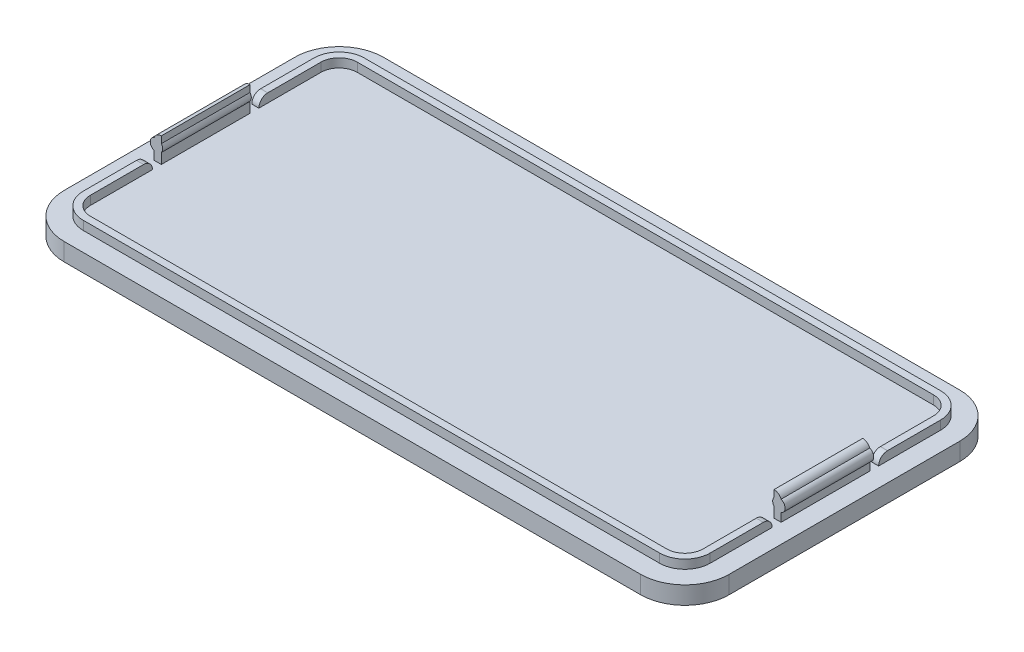
SolidWorks part; units mm, degrees
ref_plane "前视基准面" through (0, 0, 0) normal (0, 0, 1) x (1, 0, 0)
ref_plane "上视基准面" through (0, 0, 0) normal (0, 1, 0) x (1, 0, 0)
ref_plane "右视基准面" through (0, 0, 0) normal (1, 0, 0) x (0, 0, -1)
sketch "zero" plane through (0, 0, 0) normal (0, 1, 0) x (1, 0, 0)
  line L1 (-29.5, 15) -> (29.5, 15)
  line L2 (-32.5, 12) -> (-32.5, -12)
  line L3 (-29.5, -15) -> (29.5, -15)
  line L4 (32.5, 12) -> (32.5, -12)
  line L5 (-32.5, 15) -> (32.5, -15) construction
  line L6 (-32.5, -15) -> (32.5, 15) construction
  line L7 (-25.7, -15) -> (-14.5, -15)
  line L8 (-25.7, -15) -> (-25.7, -9.6569)
  line L9 (-25.7, -9.6569) -> (-14.5, -9.6569)
  line L10 (-14.5, -15) -> (-14.5, -9.6569)
  line L11 (5.2, -15) -> (12.7, -15)
  line L12 (5.2, -15) -> (5.2, -11)
  line L13 (5.2, -11) -> (12.7, -11)
  line L14 (12.7, -15) -> (12.7, -11)
  line L15 (17.8, -15) -> (25.3, -15)
  line L16 (17.8, -15) -> (17.8, -11)
  line L17 (17.8, -11) -> (25.3, -11)
  line L18 (25.3, -15) -> (25.3, -11)
  line L19 (-32.5, 7.7) -> (-19.5, 7.7)
  line L20 (-32.5, 7.7) -> (-32.5, -4.3)
  line L21 (-32.5, -4.3) -> (-19.5, -4.3)
  line L22 (-19.5, 7.7) -> (-19.5, -4.3)
  line L23 (-25.5, 14) -> (25.5, 14)
  line L24 (-25.5, 14) -> (-25.5, 8.8)
  line L25 (-25.5, 8.8) -> (25.5, 8.8)
  line L26 (25.5, 14) -> (25.5, 8.8)
  line L27 (-19.5, 7.2329) -> (-35.5, 7.2329)
  line L28 (-19.5, 7.2329) -> (-19.5, -3.7671)
  line L29 (-19.5, -3.7671) -> (-35.5, -3.7671)
  line L30 (-35.5, 7.2329) -> (-35.5, -3.7671)
  arc A0 (29.5, -15) -> (32.5, -12) centre (29.5, -12) ccw
  arc A1 (29.5, 15) -> (32.5, 12) centre (29.5, 12) cw
  arc A2 (-32.5, -12) -> (-29.5, -15) centre (-29.5, -12) ccw
  arc A3 (-29.5, 15) -> (-32.5, 12) centre (-29.5, 12) ccw
  circle A4 centre (-29, 11.4) radius 3
  circle A5 centre (-29, -11.5) radius 3
  circle A6 centre (29, 11.4) radius 3
  circle A7 centre (29, -11.5) radius 3
  circle A8 centre (-29, 11.4) radius 1.375
  circle A9 centre (-29, -11.5) radius 1.375
  circle A10 centre (29, -11.5) radius 1.375
  circle A11 centre (29, 11.4) radius 1.375
  point P0 (0, 0)
  dimension "D3" = 3
  dimension "D4" = 6
  dimension "D9" = 2.75
  dimension "D1" = 65
  dimension "D2" = 30
  dimension "D5" = 3.6
  dimension "D6" = 3.5
  dimension "D7" = 3.5
  dimension "D8" = 3.5
  dimension "D10" = 12
  dimension "D11" = 7.3
  dimension "D12" = 13
  dimension "D13" = 11.2
  dimension "D14" = 6.8
  dimension "D15" = 19.7
  dimension "D16" = 7.5
  dimension "D17" = 7.5
  dimension "D18" = 5.1
  dimension "D19" = 4
  dimension "D20" = 5.2
  dimension "D21" = 7
  dimension "D22" = 7
  dimension "D23" = 1
  dimension "D24" = 11
  dimension "D25" = 16
sketch "sugar" plane through (0, 0, 0) normal (0, 1, 0) x (1, 0, 0)
  line L1 (-29.5, 15) -> (29.5, 15)
  line L2 (-32.5, 12) -> (-32.5, -12)
  line L3 (-29.5, -15) -> (29.5, -15)
  line L4 (32.5, 12) -> (32.5, -12)
  line L5 (-32.5, 15) -> (32.5, -15) construction
  line L6 (-32.5, -15) -> (32.5, 15) construction
  line L7 (23.5, -11.5) -> (19.5, -11.5)
  line L8 (23.5, -11.5) -> (23.5, -13.9082)
  line L9 (23.5, -13.9082) -> (19.5, -13.9082)
  line L10 (19.5, -11.5) -> (19.5, -13.9082)
  line L11 (16, -11.0071) -> (8.5, -11.0071)
  line L12 (16, -11.0071) -> (16, -15)
  line L13 (16, -15) -> (8.5, -15)
  line L14 (8.5, -11.0071) -> (8.5, -15)
  line L15 (20.5, -13.9082) -> (22.5, -13.9082)
  line L16 (20.5, -13.9082) -> (20.5, -14.8173)
  line L17 (20.5, -14.8173) -> (22.5, -14.8173)
  line L18 (22.5, -13.9082) -> (22.5, -14.8173)
  arc A0 (29.5, 15) -> (32.5, 12) centre (29.5, 12) cw
  arc A1 (29.5, -15) -> (32.5, -12) centre (29.5, -12) ccw
  arc A2 (-32.5, -12) -> (-29.5, -15) centre (-29.5, -12) ccw
  arc A3 (-29.5, 15) -> (-32.5, 12) centre (-29.5, 12) ccw
  circle A4 centre (-29, 11.4) radius 3
  circle A5 centre (-29, 11.4) radius 1.375
  circle A6 centre (-29, -11.5) radius 3
  circle A7 centre (-29, -11.5) radius 1.375
  circle A8 centre (29, 11.4) radius 3
  circle A9 centre (29, 11.4) radius 1.375
  circle A10 centre (29, -11.5) radius 3
  circle A11 centre (29, -11.5) radius 1.375
  dimension "D3" = 3
  dimension "D1" = 65
  dimension "D2" = 30
  dimension "D4" = 9
  dimension "D5" = 4
  dimension "D6" = 3.5
  dimension "D7" = 7.5
  dimension "D8" = 2
  dimension "D9" = 1
sketch "case" plane through (0, 0, 0) normal (0, 1, 0) x (1, 0, 0)
  line L1 (-34.0422, 18) -> (30.9578, 18)
  line L2 (-39.0422, 13) -> (-39.0422, -13)
  line L3 (-34.0422, -18) -> (30.9578, -18)
  line L4 (35.9578, 13) -> (35.9578, -13)
  line L5 (-39.0422, 18) -> (35.9578, -18) construction
  line L6 (-39.0422, -18) -> (35.9578, 18) construction
  arc A0 (-39.0422, -13) -> (-34.0422, -18) centre (-34.0422, -13) ccw
  arc A1 (30.9578, -18) -> (35.9578, -13) centre (30.9578, -13) ccw
  arc A2 (30.9578, 18) -> (35.9578, 13) centre (30.9578, 13) cw
  arc A3 (-34.0422, 18) -> (-39.0422, 13) centre (-34.0422, 13) ccw
  point P0 (-1.5422, 0)
  point P3 (-1.5422, 0)
  dimension "D3" = 5
  dimension "D1" = 75
  dimension "D2" = 36
extrude "凸台-拉伸2" add sketch "case" along normal blind 2
sketch "草图2" plane through (0, 0, 0) normal (0, 1, 0) x (1, 0, 0)
  line L4 (-34.0422, -15.05) -> (30.9578, -15.05)
  line L5 (33.0078, -13) -> (33.0078, 13)
  line L6 (30.9578, 15.05) -> (-34.0422, 15.05)
  line L7 (-36.0922, 13) -> (-36.0922, -13)
  line L8 (33.8078, -13) -> (33.8078, 13)
  line L9 (30.9578, 15.85) -> (-34.0422, 15.85)
  line L10 (-36.8922, 13) -> (-36.8922, -13)
  line L11 (-34.0422, -15.85) -> (30.9578, -15.85)
  line L12 (33.8078, -13) -> (33.8078, 13)
  line L13 (30.9578, 15.85) -> (-34.0422, 15.85)
  line L14 (-36.8922, 13) -> (-36.8922, -13)
  line L15 (-34.0422, -15.85) -> (30.9578, -15.85)
  arc A4 (30.9578, -15.05) -> (33.0078, -13) centre (30.9578, -13) ccw
  arc A5 (33.0078, 13) -> (30.9578, 15.05) centre (30.9578, 13) ccw
  arc A6 (-34.0422, 15.05) -> (-36.0922, 13) centre (-34.0422, 13) ccw
  arc A7 (-36.0922, -13) -> (-34.0422, -15.05) centre (-34.0422, -13) ccw
  arc A8 (30.9578, -15.85) -> (33.8078, -13) centre (30.9578, -13) ccw
  arc A9 (33.8078, 13) -> (30.9578, 15.85) centre (30.9578, 13) ccw
  arc A10 (-34.0422, 15.85) -> (-36.8922, 13) centre (-34.0422, 13) ccw
  arc A11 (-36.8922, -13) -> (-34.0422, -15.85) centre (-34.0422, -13) ccw
  arc A12 (30.9578, -15.85) -> (33.8078, -13) centre (30.9578, -13) ccw
  arc A13 (33.8078, 13) -> (30.9578, 15.85) centre (30.9578, 13) ccw
  arc A14 (-34.0422, 15.85) -> (-36.8922, 13) centre (-34.0422, 13) ccw
  arc A15 (-36.8922, -13) -> (-34.0422, -15.85) centre (-34.0422, -13) ccw
  dimension "D1" = 2.15
  dimension "D2" = 0.8
ref_plane "基准面1" through (0, 2, 0) normal (0, 1, 0) x (1, 0, 0)
sketch "草图3" plane through (0, 2, 0) normal (0, 1, 0) x (1, 0, 0)
  line L4 (-34.0422, -15.05) -> (30.9578, -15.05)
  line L5 (33.0078, -13) -> (33.0078, 13)
  line L6 (30.9578, 15.05) -> (-34.0422, 15.05)
  line L7 (-36.0922, 13) -> (-36.0922, -13)
  line L8 (-34.0422, -15.05) -> (30.9578, -15.05)
  line L9 (33.0078, -13) -> (33.0078, 13)
  line L10 (30.9578, 15.05) -> (-34.0422, 15.05)
  line L11 (-36.0922, 13) -> (-36.0922, -13)
  line L12 (-36.8922, 13) -> (-36.8922, -13)
  line L13 (-34.0422, -15.85) -> (30.9578, -15.85)
  line L14 (33.8078, -13) -> (33.8078, 13)
  line L15 (30.9578, 15.85) -> (-34.0422, 15.85)
  line L16 (-36.8922, 13) -> (-36.8922, -13)
  line L17 (-34.0422, -15.85) -> (30.9578, -15.85)
  line L18 (33.8078, -13) -> (33.8078, 13)
  line L19 (30.9578, 15.85) -> (-34.0422, 15.85)
  arc A4 (30.9578, -15.05) -> (33.0078, -13) centre (30.9578, -13) ccw
  arc A5 (33.0078, 13) -> (30.9578, 15.05) centre (30.9578, 13) ccw
  arc A6 (-34.0422, 15.05) -> (-36.0922, 13) centre (-34.0422, 13) ccw
  arc A7 (-36.0922, -13) -> (-34.0422, -15.05) centre (-34.0422, -13) ccw
  arc A8 (30.9578, -15.05) -> (33.0078, -13) centre (30.9578, -13) ccw
  arc A9 (33.0078, 13) -> (30.9578, 15.05) centre (30.9578, 13) ccw
  arc A10 (-34.0422, 15.05) -> (-36.0922, 13) centre (-34.0422, 13) ccw
  arc A11 (-36.0922, -13) -> (-34.0422, -15.05) centre (-34.0422, -13) ccw
  arc A12 (-36.8922, -13) -> (-34.0422, -15.85) centre (-34.0422, -13) ccw
  arc A13 (30.9578, -15.85) -> (33.8078, -13) centre (30.9578, -13) ccw
  arc A14 (33.8078, 13) -> (30.9578, 15.85) centre (30.9578, 13) ccw
  arc A15 (-34.0422, 15.85) -> (-36.8922, 13) centre (-34.0422, 13) ccw
  arc A16 (-36.8922, -13) -> (-34.0422, -15.85) centre (-34.0422, -13) ccw
  arc A17 (30.9578, -15.85) -> (33.8078, -13) centre (30.9578, -13) ccw
  arc A18 (33.8078, 13) -> (30.9578, 15.85) centre (30.9578, 13) ccw
  arc A19 (-34.0422, 15.85) -> (-36.8922, 13) centre (-34.0422, 13) ccw
  dimension "D1" = 0
  dimension "D2" = 0
extrude "凸台-拉伸4" add sketch "草图3" along normal blind 1
ref_plane "基准面3" through (33.8078, 0, 0) normal (1, 0, 0) x (0, 0, -1)
sketch "草图7" plane through (0, 2, 0) normal (0, 1, 0) x (1, 0, 0)
  line L0 (-36.8922, 13) -> (-36.8922, -13) construction
  line L1 (-36.8922, 5) -> (-36.0922, 5)
  line L2 (-36.8922, 5) -> (-36.8922, -5)
  line L3 (-36.8922, -5) -> (-36.0922, -5)
  line L4 (-36.0922, 5) -> (-36.0922, -5)
  line L5 (-36.0922, 13) -> (-36.0922, -13) construction
  point P10 (-36.0922, 0)
  dimension "D1" = 5
  dimension "D2" = 10
extrude "凸台-拉伸8" add sketch "草图7" along normal blind 2.8
ref_plane "基准面5" through (0, 0, 5) normal (0, 0, 1) x (1, 0, 0)
sketch "草图8" plane through (0, 0, 5) normal (0, 0, 1) x (1, 0, 0)
  line L0 (-34.0422, 2) -> (-39.0422, 2) construction
  line L1 (-36.8922, 4.8) -> (-36.8922, 3) construction
  circle A0 centre (-36.6422, 3.6) radius 0.7
  dimension "D1" = 1.4
  dimension "D2" = 1.6
  dimension "D3" = 0.25
extrude "凸台-拉伸9" add sketch "草图8" against normal blind 10
fillet "圆角1" radius 0.85 1 edges at (-36.8922, 4.8, 0)
ref_plane "基准面7" through (-36.8922, 0, 0) normal (-1, 0, 0) x (0, 0, 1)
sketch "草图11" plane through (-36.8922, 0, 0) normal (-1, 0, 0) x (0, 0, 1)
  line L0 (-13, 2) -> (13, 2) construction
  line L1 (5, 3) -> (6, 3)
  line L2 (5, 3) -> (5, 2)
  line L3 (5, 2) -> (6, 2)
  line L4 (6, 3) -> (6, 2)
  line L6 (-5, 3) -> (-6, 3)
  line L7 (-5, 3) -> (-5, 2)
  line L8 (-5, 2) -> (-6, 2)
  line L9 (-6, 3) -> (-6, 2)
  dimension "D1" = 1
  dimension "D2" = 1
extrude "切除-拉伸1" cut sketch "草图11" against normal blind 1.2
fillet "圆角2" radius 1 2 edges at (-36.4922, 3, 6) (-36.4922, 3, -6)
ref_plane "基准面8" through (0, 0, 0) normal (0, -1, 0) x (-1, 0, 0)
sketch "草图12" plane through (0, 0, 0) normal (0, -1, 0) x (-1, 0, 0)
  line L76 (34.0422, -18) -> (-30.9578, -18) construction
  line L78 (39.0422, 13) -> (39.0422, -13) construction
  line B0 (-8.1993, 5.026) -> (-9.0198, 5.499)
  line B1 (-9.0198, 5.499) -> (-13.2767, 7.9551)
  line B2 (-13.2767, 7.9551) -> (-14.0973, 8.4339)
  line B3 (-15.8183, 8.4339) -> (-16.6389, 7.9551)
  line B4 (-16.6389, 7.9551) -> (-20.8958, 5.499)
  line B5 (-20.8958, 5.499) -> (-21.7165, 5.026)
  line B6 (-22.577, 3.5387) -> (-22.577, -3.2769)
  line B7 (-21.7165, -4.7643) -> (-20.8958, -5.2373)
  line B8 (-20.8958, -5.2373) -> (-16.6389, -7.6934)
  line B9 (-16.6389, -7.6934) -> (-15.8183, -8.172)
  line B10 (-14.0973, -8.172) -> (-13.2767, -7.6934)
  line B11 (-13.2767, -7.6934) -> (-9.0198, -5.2373)
  line B12 (-9.0198, -5.2373) -> (-8.1993, -4.7643)
  line B13 (-7.3388, -3.2769) -> (-7.3388, 3.5387)
  line B14 (-20.6223, 4.3479) -> (-15.3568, 7.391)
  line B15 (-14.5532, 7.391) -> (-9.3162, 4.3422)
  line B16 (-9.3105, 3.6413) -> (-14.3993, 0.5982)
  line B17 (-12.8208, -4.5591) -> (-13.4135, -4.8896)
  line B18 (-13.4705, -4.9865) -> (-13.4705, -6.6961)
  line B19 (-13.5274, -6.793) -> (-14.633, -7.4198)
  line B20 (-14.7983, -7.3229) -> (-14.7983, -2.046)
  line B21 (-14.7413, -1.9491) -> (-12.8607, -0.8835)
  line B22 (-8.9173, -4.2058) -> (-10.0114, -4.8269)
  line B23 (-10.1767, -4.7301) -> (-10.1767, -2.2169)
  line B24 (-10.1197, -2.1201) -> (-9.0256, -1.5046)
  line B25 (-8.8603, -1.6015) -> (-8.8603, -4.1089)
  line B26 (-12.8893, -3.5447) -> (-13.4135, -3.8069)
  line B27 (-13.4705, -3.6872) -> (-13.4705, -2.3423)
  line B28 (-13.4135, -2.2455) -> (-12.9234, -1.9719)
  line B29 (-3.344, 3.06) -> (-5.2189, 3.06)
  line B30 (-5.2189, 3.06) -> (-5.2189, -3.5048)
  line B31 (-5.2189, -3.5048) -> (-4.3868, -3.5048)
  line B32 (-4.3868, -3.5048) -> (-4.3868, -0.9005)
  line B33 (-4.3868, -0.9005) -> (-3.2984, -0.9005)
  line B34 (-3.4066, -0.2281) -> (-4.3868, -0.2281)
  line B35 (-4.3868, -0.2281) -> (-4.3868, 2.3876)
  line B36 (-4.3868, 2.3876) -> (-3.4408, 2.3876)
  line B37 (0.1948, 1.3618) -> (0.1948, -3.5048)
  line B38 (0.1948, -3.5048) -> (1.0098, -3.5048)
  line B39 (1.0098, -3.5048) -> (1.0098, 1.3618)
  line B40 (1.0098, 1.3618) -> (0.1948, 1.3618)
  line B41 (5.7169, 0.2847) -> (4.8849, 0.6153)
  line B42 (6.0417, 1.4017) -> (6.8396, 2.4047)
  line B43 (3.6084, -0.5586) -> (4.4575, -0.9177)
  line B44 (2.9074, -1.5673) -> (2.0014, -2.6729)
  line B45 (10.8229, 1.5898) -> (10.8229, -1.7497)
  line B46 (9.3811, -1.3621) -> (9.3811, 1.5898)
  line B47 (9.3811, 1.5898) -> (7.7912, 1.5898)
  line B48 (7.7912, 1.5898) -> (7.7912, -1.5616)
  line B49 (10.9711, -2.8039) -> (11.0052, -2.8039)
  line B50 (11.0052, -2.8039) -> (11.1193, -3.5048)
  line B51 (11.1193, -3.5048) -> (12.4185, -3.5048)
  line B52 (12.4185, -3.5048) -> (12.4185, 1.5898)
  line B53 (12.4185, 1.5898) -> (10.8229, 1.5898)
  line B54 (16.2708, -2.5019) -> (15.4673, -2.5019)
  line B55 (17.365, 0.4386) -> (18.1513, 0.4386)
  line B56 (18.1513, 0.4386) -> (18.1513, 1.5898)
  line B57 (18.1513, 1.5898) -> (16.2822, 1.5898)
  line B58 (14.0312, -1.4533) -> (14.0312, -1.4875)
  line B59 (13.9344, -3.3168) -> (13.9344, -3.3624)
  line B60 (15.4844, -3.7214) -> (15.9688, -3.7214)
  line B61 (18.6072, 1.0484) -> (19.1657, -0.0002)
  line B62 (21.411, -2.992) -> (21.4508, -2.992)
  line B63 (21.4508, -2.992) -> (21.5648, -3.5048)
  line B64 (21.5648, -3.5048) -> (22.8641, -3.5048)
  line B65 (22.8641, -3.5048) -> (22.8641, -0.6099)
  line B66 (21.2685, -1.1741) -> (21.2685, -1.989)
  line B67 (25.3545, 0.7065) -> (25.3203, 0.7065)
  line B68 (25.3203, 0.7065) -> (25.212, 1.5898)
  line B69 (25.212, 1.5898) -> (23.9127, 1.5898)
  line B70 (23.9127, 1.5898) -> (23.9127, -3.5048)
  line B71 (23.9127, -3.5048) -> (25.4969, -3.5048)
  line B72 (25.4969, -3.5048) -> (25.4969, -0.5928)
  line B73 (27.1552, 0.2392) -> (27.423, 1.6125)
  line B74 (-13.4135, -3.8069) -> (-13.4135, -4.8896)
  line B75 (-13.4705, -3.6872) -> (-13.4705, -4.9865)
  spline B76 degree 3 poles (-14.0973, 8.4339) (-14.3652, 8.582) (-14.6615, 8.6618) (-14.9578, 8.6618) knots 3 3 3 3 4 4 4 4
  spline B77 degree 3 poles (-14.9578, 8.6618) (-15.2541, 8.6618) (-15.5505, 8.582) (-15.8183, 8.4339) knots 4 4 4 4 5 5 5 5
  spline B78 degree 3 poles (-21.7165, 5.026) (-22.2464, 4.7183) (-22.577, 4.1485) (-22.577, 3.5387) knots 8 8 8 8 9 9 9 9
  spline B79 degree 3 poles (-22.577, -3.2769) (-22.577, -3.8923) (-22.2464, -4.4565) (-21.7165, -4.7643) knots 10 10 10 10 11 11 11 11
  spline B80 degree 3 poles (-15.8183, -8.172) (-15.5505, -8.3259) (-15.2541, -8.4) (-14.9578, -8.4) knots 14 14 14 14 15 15 15 15
  spline B81 degree 3 poles (-14.9578, -8.4) (-14.6615, -8.4) (-14.3652, -8.3259) (-14.0973, -8.172) knots 15 15 15 15 16 16 16 16
  spline B82 degree 3 poles (-8.1993, -4.7643) (-7.6636, -4.4565) (-7.3388, -3.8923) (-7.3388, -3.2769) knots 19 19 19 19 20 20 20 20
  spline B83 degree 3 poles (-7.3388, 3.5387) (-7.3388, 4.1485) (-7.6636, 4.7183) (-8.1993, 5.026) knots 21 21 21 21 22 22 22 22
  spline B84 degree 2 poles (-15.5106, 0.5982) (-20.6622, 3.5729) (-20.6736, 3.5786) knots 0 0 0 1 1 1
  spline B85 degree 3 poles (-20.6736, 3.5786) (-20.9414, 3.7723) (-20.9129, 4.1826) (-20.6223, 4.3479) knots 1 1 1 1 2 2 2 2
  spline B86 degree 3 poles (-15.3568, 7.391) (-15.1117, 7.5335) (-14.8039, 7.5335) (-14.5532, 7.391) knots 3 3 3 3 4 4 4 4
  spline B87 degree 3 poles (-9.3162, 4.3422) (-9.0484, 4.1883) (-9.0427, 3.8008) (-9.3105, 3.6413) knots 5 5 5 5 6 6 6 6
  spline B88 degree 3 poles (-14.3993, 0.5982) (-14.7413, 0.3987) (-15.1687, 0.3987) (-15.5106, 0.5982) knots 7 7 7 7 8 8 8 8
  spline B89 degree 3 poles (-13.4705, -6.6961) (-13.4705, -6.736) (-13.4876, -6.7702) (-13.5274, -6.793) knots 3 3 3 3 4 4 4 4
  spline B90 degree 3 poles (-14.633, -7.4198) (-14.7071, -7.4597) (-14.7983, -7.4084) (-14.7983, -7.3229) knots 5 5 5 5 6 6 6 6
  spline B91 degree 3 poles (-14.7983, -2.046) (-14.7983, -2.0061) (-14.7812, -1.9662) (-14.7413, -1.9491) knots 7 7 7 7 8 8 8 8
  spline B92 degree 3 poles (-12.8607, -0.8835) (-11.6412, -0.1939) (-10.6326, -0.0572) (-10.6326, -1.4249) knots 9 9 9 9 10 10 10 10
  spline B93 degree 3 poles (-10.6326, -1.4249) (-10.6326, -2.7412) (-11.6526, -3.898) (-12.8208, -4.5591) knots 10 10 10 10 11 11 11 11
  spline B94 degree 3 poles (-8.8603, -4.1089) (-8.8603, -4.1488) (-8.8831, -4.1887) (-8.9173, -4.2058) knots 0 0 0 0 1 1 1 1
  spline B95 degree 3 poles (-10.0114, -4.8269) (-10.0855, -4.8668) (-10.1767, -4.8155) (-10.1767, -4.7301) knots 2 2 2 2 3 3 3 3
  spline B96 degree 3 poles (-10.1767, -2.2169) (-10.1767, -2.1771) (-10.1539, -2.1429) (-10.1197, -2.1201) knots 4 4 4 4 5 5 5 5
  spline B97 degree 3 poles (-9.0256, -1.5046) (-8.9515, -1.4647) (-8.8603, -1.516) (-8.8603, -1.6015) knots 6 6 6 6 7 7 7 7
  spline B98 degree 3 poles (-9.5156, 0.1651) (-9.0768, 0.4158) (-8.7634, 0.3076) (-8.7634, -0.0914) (-8.7634, -0.4846) (-9.0768, -0.9461) (-9.5156, -1.1912) knots 2 2 2 2 3 3 3 4 4 4 4
  spline B99 degree 3 poles (-9.5156, -1.1912) (-9.9601, -1.4476) (-10.2735, -1.3394) (-10.2735, -0.9461) (-10.2735, -0.5415) (-9.9601, -0.0856) (-9.5156, 0.1651) knots 0 0 0 0 1 1 1 2 2 2 2
  spline B100 degree 3 poles (-11.9319, -2.16) (-11.9319, -2.7013) (-12.2395, -3.18) (-12.8893, -3.5447) knots 0 0 0 0 1 1 1 1
  spline B101 degree 3 poles (-13.4705, -2.3423) (-13.4705, -2.3024) (-13.4477, -2.2625) (-13.4135, -2.2455) knots 4 4 4 4 5 5 5 5
  spline B102 degree 3 poles (-12.9234, -1.9719) (-12.2852, -1.6072) (-11.9319, -1.6015) (-11.9319, -2.16) knots 6 6 6 6 7 7 7 7
  spline B103 degree 3 poles (-3.2984, -0.9005) (-1.868, -0.9005) (-0.8822, -0.2509) (-0.8822, 1.1339) knots 5 5 5 5 6 6 6 6
  spline B104 degree 3 poles (-0.8822, 1.1339) (-0.8822, 2.5699) (-1.868, 3.06) (-3.344, 3.06) knots 6 6 6 6 7 7 7 7
  spline B105 degree 3 poles (-3.4408, 2.3876) (-2.2897, 2.3876) (-1.7084, 2.0855) (-1.7084, 1.1339) knots 3 3 3 3 4 4 4 4
  spline B106 degree 3 poles (-1.7084, 1.1339) (-1.7084, 0.1936) (-2.2498, -0.2281) (-3.4066, -0.2281) knots 4 4 4 4 5 5 5 5
  spline B107 degree 3 poles (0.6052, 2.3648) (0.93, 2.3648) (1.1694, 2.587) (1.1694, 2.889) (1.1694, 3.2253) (0.93, 3.419) (0.6052, 3.419) knots 2 2 2 2 3 3 3 4 4 4 4
  spline B108 degree 3 poles (0.6052, 3.419) (0.2804, 3.419) (0.041, 3.2253) (0.041, 2.889) (0.041, 2.587) (0.2804, 2.3648) (0.6052, 2.3648) knots 0 0 0 0 1 1 1 2 2 2 2
  spline B109 degree 3 poles (4.8849, 0.6153) (4.2979, 0.8489) (3.8762, 0.9914) (3.8762, 1.3618) knots 1 1 1 1 2 2 2 2
  spline B110 degree 3 poles (3.8762, 1.3618) (3.8762, 1.7151) (4.1783, 1.9146) (4.674, 1.9146) knots 2 2 2 2 3 3 3 3
  spline B111 degree 3 poles (4.674, 1.9146) (5.1926, 1.9146) (5.6029, 1.7379) (6.0417, 1.4017) knots 3 3 3 3 4 4 4 4
  spline B112 degree 3 poles (6.8396, 2.4047) (6.2583, 2.9916) (5.4433, 3.2879) (4.674, 3.2879) knots 5 5 5 5 6 6 6 6
  spline B113 degree 3 poles (4.674, 3.2879) (3.2551, 3.2879) (2.2521, 2.3876) (2.2521, 1.2706) knots 6 6 6 6 7 7 7 7
  spline B114 degree 3 poles (2.2521, 1.2706) (2.2521, 0.3019) (2.9074, -0.2794) (3.6084, -0.5586) knots 7 7 7 7 8 8 8 8
  spline B115 degree 3 poles (4.4575, -0.9177) (5.0274, -1.157) (5.3978, -1.2824) (5.3978, -1.6699) knots 9 9 9 9 10 10 10 10
  spline B116 degree 3 poles (5.3978, -1.6699) (5.3978, -2.0289) (5.1185, -2.2511) (4.5259, -2.2511) knots 10 10 10 10 11 11 11 11
  spline B117 degree 3 poles (4.5259, -2.2511) (4.0016, -2.2511) (3.3804, -1.9719) (2.9074, -1.5673) knots 11 11 11 11 12 12 12 12
  spline B118 degree 3 poles (2.0014, -2.6729) (2.6909, -3.3054) (3.6254, -3.6302) (4.4916, -3.6302) knots 13 13 13 13 14 14 14 14
  spline B119 degree 3 poles (4.4916, -3.6302) (6.1044, -3.6302) (7.0389, -2.6557) (7.0389, -1.5445) knots 14 14 14 14 15 15 15 15
  spline B120 degree 3 poles (7.0389, -1.5445) (7.0389, -0.6042) (6.5432, -0.0458) (5.7169, 0.2847) knots 15 15 15 15 16 16 16 16
  spline B121 degree 3 poles (10.8229, -1.7497) (10.5551, -2.1258) (10.3328, -2.2682) (9.9738, -2.2682) knots 1 1 1 1 2 2 2 2
  spline B122 degree 3 poles (9.9738, -2.2682) (9.5692, -2.2682) (9.3811, -2.0688) (9.3811, -1.3621) knots 2 2 2 2 3 3 3 3
  spline B123 degree 3 poles (7.7912, -1.5616) (7.7912, -2.8324) (8.2642, -3.6302) (9.3754, -3.6302) knots 6 6 6 6 7 7 7 7
  spline B124 degree 3 poles (9.3754, -3.6302) (10.0706, -3.6302) (10.5494, -3.3054) (10.9711, -2.8039) knots 7 7 7 7 8 8 8 8
  spline B125 degree 3 poles (15.4673, -2.5019) (14.9202, -2.5019) (14.7151, -2.3936) (14.7151, -2.16) knots 1 1 1 1 2 2 2 2
  spline B126 degree 3 poles (14.7151, -2.16) (14.7151, -1.989) (14.7549, -1.9092) (14.8746, -1.8009) knots 2 2 2 2 3 3 3 3
  spline B127 degree 3 poles (14.8746, -1.8009) (15.0969, -1.8636) (15.302, -1.8921) (15.473, -1.8921) knots 3 3 3 3 4 4 4 4
  spline B128 degree 3 poles (15.473, -1.8921) (16.6013, -1.8921) (17.5074, -1.3735) (17.5074, -0.1825) knots 4 4 4 4 5 5 5 5
  spline B129 degree 3 poles (17.5074, -0.1825) (17.5074, 0.0625) (17.4447, 0.2962) (17.365, 0.4386) knots 5 5 5 5 6 6 6 6
  spline B130 degree 3 poles (16.2822, 1.5898) (16.0485, 1.6752) (15.7693, 1.7151) (15.473, 1.7151) knots 9 9 9 9 10 10 10 10
  spline B131 degree 3 poles (15.473, 1.7151) (14.3732, 1.7151) (13.3417, 1.1111) (13.3417, -0.1369) knots 10 10 10 10 11 11 11 11
  spline B132 degree 3 poles (13.3417, -0.1369) (13.3417, -0.7296) (13.6722, -1.2026) (14.0312, -1.4533) knots 11 11 11 11 12 12 12 12
  spline B133 degree 3 poles (14.0312, -1.4875) (13.7007, -1.7212) (13.467, -2.0802) (13.467, -2.4392) knots 13 13 13 13 14 14 14 14
  spline B134 degree 3 poles (13.467, -2.4392) (13.467, -2.8666) (13.6665, -3.1344) (13.9344, -3.3168) knots 14 14 14 14 15 15 15 15
  spline B135 degree 3 poles (13.9344, -3.3624) (13.4613, -3.6017) (13.2106, -3.9436) (13.2106, -4.3653) knots 16 16 16 16 17 17 17 17
  spline B136 degree 3 poles (13.2106, -4.3653) (13.2106, -5.2771) (14.1737, -5.6475) (15.3476, -5.6475) knots 17 17 17 17 18 18 18 18
  spline B137 degree 3 poles (15.3476, -5.6475) (17.1199, -5.6475) (18.2312, -4.8839) (18.2312, -3.8069) knots 18 18 18 18 19 19 19 19
  spline B138 degree 3 poles (18.2312, -3.8069) (18.2312, -2.8837) (17.5245, -2.5019) (16.2708, -2.5019) knots 19 19 19 19 20 20 20 20
  spline B139 degree 3 poles (15.473, -0.9347) (15.1083, -0.9347) (14.8291, -0.6669) (14.8291, -0.1369) (14.8291, 0.3816) (15.1083, 0.6495) (15.473, 0.6495) knots 2 2 2 2 3 3 3 4 4 4 4
  spline B140 degree 3 poles (15.473, 0.6495) (15.8491, 0.6495) (16.1169, 0.3816) (16.1169, -0.1369) (16.1169, -0.6669) (15.8491, -0.9347) (15.473, -0.9347) knots 0 0 0 0 1 1 1 2 2 2 2
  spline B141 degree 3 poles (15.5983, -4.6503) (14.943, -4.6503) (14.5156, -4.4736) (14.5156, -4.1146) knots 0 0 0 0 1 1 1 1
  spline B142 degree 3 poles (14.5156, -4.1146) (14.5156, -3.9436) (14.5953, -3.8012) (14.7549, -3.6587) knots 1 1 1 1 2 2 2 2
  spline B143 degree 3 poles (14.7549, -3.6587) (14.9202, -3.7043) (15.114, -3.7214) (15.4844, -3.7214) knots 2 2 2 2 3 3 3 3
  spline B144 degree 3 poles (15.9688, -3.7214) (16.4417, -3.7214) (16.7096, -3.7841) (16.7096, -4.0861) knots 4 4 4 4 5 5 5 5
  spline B145 degree 3 poles (16.7096, -4.0861) (16.7096, -4.4109) (16.2537, -4.6503) (15.5983, -4.6503) knots 5 5 5 5 6 6 6 6
  spline B146 degree 3 poles (20.8013, 1.7151) (20.0091, 1.7151) (19.2797, 1.4473) (18.6072, 1.0484) knots 0 0 0 0 1 1 1 1
  spline B147 degree 3 poles (19.1657, -0.0002) (19.6729, 0.2847) (20.0946, 0.4443) (20.4992, 0.4443) knots 2 2 2 2 3 3 3 3
  spline B148 degree 3 poles (20.4992, 0.4443) (21.0177, 0.4443) (21.2344, 0.205) (21.2685, -0.2053) knots 3 3 3 3 4 4 4 4
  spline B149 degree 3 poles (21.2685, -0.2053) (19.2797, -0.4219) (18.4362, -1.0031) (18.4362, -2.0802) knots 4 4 4 4 5 5 5 5
  spline B150 degree 3 poles (18.4362, -2.0802) (18.4362, -2.9293) (19.0118, -3.6302) (19.9522, -3.6302) knots 5 5 5 5 6 6 6 6
  spline B151 degree 3 poles (19.9522, -3.6302) (20.5163, -3.6302) (20.9893, -3.3681) (21.411, -2.992) knots 6 6 6 6 7 7 7 7
  spline B152 degree 3 poles (22.8641, -0.6099) (22.8641, 0.9857) (22.1176, 1.7151) (20.8013, 1.7151) knots 11 11 11 11 12 12 12 12
  spline B153 degree 3 poles (21.2685, -1.989) (21.0349, -2.2398) (20.824, -2.3936) (20.4992, -2.3936) knots 0 0 0 0 1 1 1 1
  spline B154 degree 3 poles (20.4992, -2.3936) (20.1686, -2.3936) (19.9522, -2.2511) (19.9522, -1.9548) knots 1 1 1 1 2 2 2 2
  spline B155 degree 3 poles (19.9522, -1.9548) (19.9522, -1.5958) (20.277, -1.3109) (21.2685, -1.1741) knots 2 2 2 2 3 3 3 3
  spline B156 degree 3 poles (26.8076, 1.7151) (26.2947, 1.7151) (25.7305, 1.3846) (25.3545, 0.7065) knots 0 0 0 0 1 1 1 1
  spline B157 degree 3 poles (25.4969, -0.5928) (25.7648, 0.0796) (26.2207, 0.3189) (26.5967, 0.3189) knots 7 7 7 7 8 8 8 8
  spline B158 degree 3 poles (26.5967, 0.3189) (26.8247, 0.3189) (26.9729, 0.2847) (27.1552, 0.2392) knots 8 8 8 8 9 9 9 9
  spline B159 degree 3 poles (27.423, 1.6125) (27.2806, 1.6752) (27.1096, 1.7151) (26.8076, 1.7151) knots 10 10 10 10 11 11 11 11
  dimension "D1" = 9.6
  dimension "D2" = 54
sketch_block_instance "块1-1"
sketch_block "块1"
extrude "切除-拉伸2" cut sketch "草图12" against normal blind 0.5
sketch "草图13" plane through (0, 3, 0) normal (0, 1, 0) x (1, 0, 0)
  line L0 (33.0078, -13) -> (33.0078, 13) construction
  line L1 (33.0078, 5) -> (33.8078, 5)
  line L2 (33.0078, 5) -> (33.0078, -5)
  line L3 (33.0078, -5) -> (33.8078, -5)
  line L4 (33.8078, 5) -> (33.8078, -5)
  line L5 (33.8078, -13) -> (33.8078, 13) construction
  line L7 (35.9578, -13) -> (35.9578, 13) construction
  point P12 (35.9578, 0)
  point P13 (33.8078, 0)
  dimension "D1" = 10
extrude "凸台-拉伸10" add sketch "草图13" along normal blind 1.8
sketch "草图14" plane through (0, 0, 5) normal (0, 0, 1) x (1, 0, 0)
  line L0 (33.8078, 2) -> (30.9578, 2) construction
  line L1 (33.8078, 4.8) -> (33.8078, 3) construction
  circle A0 centre (33.5578, 3.6) radius 0.7
  dimension "D2" = 1.4
  dimension "D1" = 1.6
  dimension "D3" = 0.25
extrude "凸台-拉伸11" add sketch "草图14" against normal blind 10
fillet "圆角3" radius 0.85 1 edges at (33.8078, 4.8, 0)
sketch "草图15" plane through (0, 3, 0) normal (0, 1, 0) x (1, 0, 0)
  line L0 (33.8078, 5) -> (33.8078, 13) construction
  line L1 (33.0078, 5) -> (33.8078, 5)
  line L2 (33.0078, 5) -> (33.0078, 6)
  line L3 (33.0078, 6) -> (33.8078, 6)
  line L4 (33.8078, 5) -> (33.8078, 6)
  line L5 (33.8078, -13) -> (33.8078, -5) construction
  line L6 (33.0078, -5) -> (33.8078, -5)
  line L7 (33.0078, -5) -> (33.0078, -6)
  line L8 (33.0078, -6) -> (33.8078, -6)
  line L9 (33.8078, -5) -> (33.8078, -6)
  dimension "D1" = 1
  dimension "D2" = 1
extrude "切除-拉伸3" cut sketch "草图15" against normal blind 1
fillet "圆角4" radius 1 2 edges at (33.4078, 3, 6) (33.4078, 3, -6)
